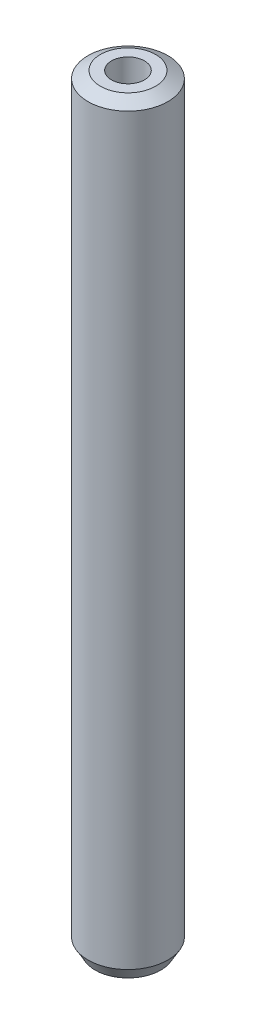
SolidWorks part; units mm, degrees
ref_plane "Front Plane" through (0, 0, 0) normal (0, 0, 1) x (1, 0, 0)
ref_plane "Top Plane" through (0, 0, 0) normal (0, 1, 0) x (1, 0, 0)
ref_plane "Right Plane" through (0, 0, 0) normal (1, 0, 0) x (0, 0, -1)
sketch "Sketch1" plane through (0, 0, 0) normal (0, 1, 0) x (1, 0, 0)
  circle A0 centre (0, 0) radius 10
  dimension "SHAFT_OD" = 20
extrude "Boss-Extrude1" add sketch "Sketch1" along normal blind 191.0756
sketch "Sketch2" plane through (0, 0, 0) normal (0, 1, 0) x (1, 0, 0)
  circle A0 centre (0, 0) radius 4.1334
  dimension "BORE_D" = 8.2668
extrude "Cut-Extrude1" cut sketch "Sketch2" along normal through all
chamfer "Chamfer1" distance 1.786 angle 60 2 edges at (0, 191.0756, 10) (0, 0, 10) first distance on face at (0, 191.0756, 10) first distance on face at (0, 0, 4.1334)
